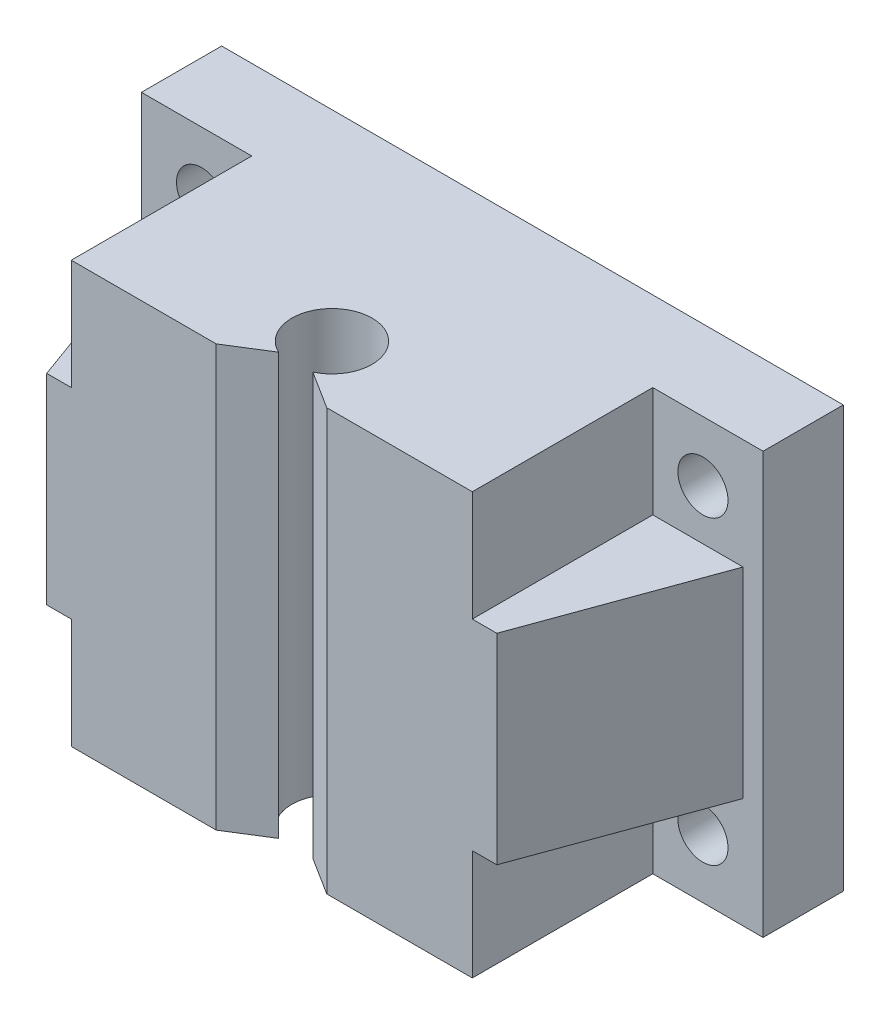
SolidWorks part; units mm, degrees
material "1060 Alloy"
ref_plane "Front Plane" through (0, 0, 0) normal (0, 0, 1) x (1, 0, 0)
ref_plane "Top Plane" through (0, 0, 0) normal (0, 1, 0) x (1, 0, 0)
ref_plane "Right Plane" through (0, 0, 0) normal (1, 0, 0) x (0, 0, -1)
sketch "Sketch1" plane through (0, 0, 0) normal (0, 1, 0) x (1, 0, 0)
  line L0 (20, -4) -> (31, -4)
  line L1 (-31, -4) -> (-20, -4)
  line L2 (-31, -4) -> (-31, 4)
  line L3 (-31, 4) -> (31, 4)
  line L4 (31, -4) -> (31, 4)
  line L5 (29, -4) -> (22.4485, -22)
  line L6 (-29, -4) -> (-22.4485, -22)
  line L7 (1.7088, -19.6166) -> (5.483, -22)
  line L8 (-20, -4) -> (-20, -22)
  line L9 (-22.4485, -22) -> (-5.5468, -22)
  line L10 (20, -4) -> (20, -22)
  line L11 (-1.7246, -19.6091) -> (-5.5468, -22)
  line L12 (5.483, -22) -> (22.4485, -22)
  arc A0 (1.7088, -19.6166) -> (-1.7246, -19.6091) centre (0, -16) ccw
  point P0 (0, 0)
  dimension "D12" = 4
  dimension "D1" = 62
  dimension "D2" = 8
  dimension "D3" = 26
  dimension "D4" = 18
  dimension "D5" = 40
  dimension "D6" = 11
  dimension "D7" = 2
  dimension "D8" = 2
  dimension "D9" = 70
  dimension "D10" = 70
  dimension "D11" = 20
extrude "Extrude1" add sketch "Sketch1" along normal blind 21 and the other way blind 21 contours A0 L7 L12 L10 L0 L4 L3 L2 L1 L8 L9 L11 region at (0.0004, 0, 7.1436)
extrude "Extrude2" add sketch "Sketch1<8>" along normal blind 10 and the other way blind 10 contours L10 L12 L5 L0 | L6 L9 L8 L1 region at (23.1746, 0, 11.2832) region at (-23.1746, 0, 11.2832)
sketch "Sketch1<8>" plane through (0, 0, 0) normal (0, 1, 0) x (1, 0, 0) same geometry as "Sketch1"
sketch "Croquis1" plane through (0, 0, -4) normal (0, 0, -1) x (-1, 0, 0)
  line L1 (25, -15) -> (-25, -15) construction
  line L2 (25, -15) -> (25, 15) construction
  line L3 (25, 15) -> (-25, 15) construction
  line L4 (-25, -15) -> (-25, 15) construction
  line L5 (25, -15) -> (-25, 15) construction
  line L6 (25, 15) -> (-25, -15) construction
  circle A0 centre (-25, 15) radius 2.5
  circle A1 centre (25, 15) radius 2.5
  circle A2 centre (-25, -15) radius 2.5
  circle A3 centre (25, -15) radius 2.5
  point P0 (0, 0)
  dimension "D3" = 5
  dimension "D1" = 50
  dimension "D2" = 30
extrude "Cortar-Extruir1" cut sketch "Croquis1" against normal up to next
equation "\"D6@Sketch1\" =( \"D1@Sketch1\"-\"D5@Sketch1\")/2"
